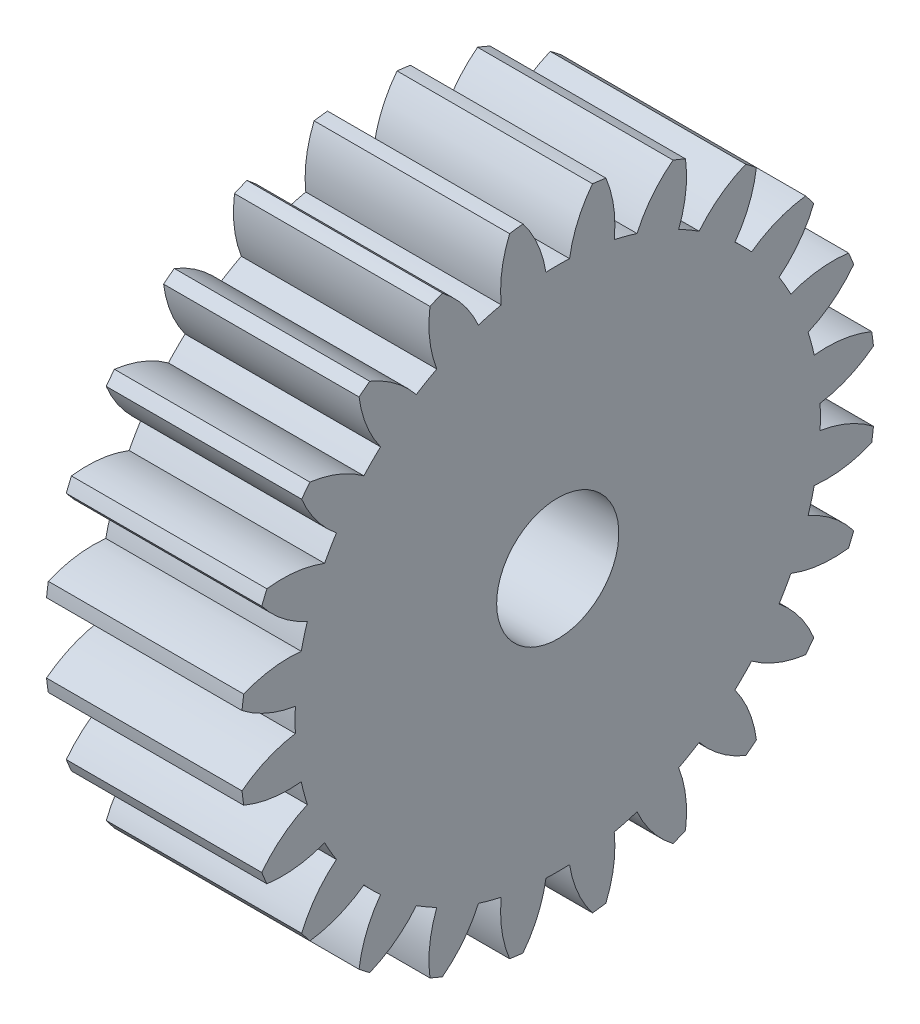
SolidWorks part; units mm, degrees
ref_plane "Plane1" through (0, 0, 0) normal (0, 0, 1) x (1, 0, 0)
ref_plane "Plane2" through (0, 0, 0) normal (0, 1, 0) x (1, 0, 0)
ref_plane "Plane3" through (0, 0, 0) normal (1, 0, 0) x (0, 0, -1)
sketch "HoldingSke" plane through (0, 0, 0) normal (0, 1, 0) x (1, 0, 0)
  line L0 (0, 0) -> (0.9135, -0.4067)
  line L1 (-15, 0) -> (100, 0) construction
  line L2 (0, 0) -> (-2.1039, 2.3779)
  line L3 (0, 0) -> (-11.863, 4.5341)
  line L4 (0, 0) -> (7.8894, 3.5126)
  line L5 (0, 0) -> (-46.8476, -17.4728)
  line L6 (0, 0) -> (-6.6317, -4.4744)
  line L7 (-2.1039, 2.3779) -> (8.6586, 51.2059)
  line L8 (-76.2, 54.61) -> (-75.3, 54.61)
  line L9 (-71.009, 38.7566) -> (-53.1078, 45.2721)
  line L10 (-76.2, 71.12) -> (104.1128, 71.12)
  line L11 (0, 0) -> (-8, 0)
  line L12 (-76.2, 101.6) -> (-76.162, 101.6)
  line L13 (24.9733, 27.94) -> (52.9518, 28.4284)
  line L14 (24.9733, 27.94) -> (24.9743, 27.94)
  line L15 (24.9733, 27.94) -> (100.4006, 29.5858)
  line L16 (-63.627, -1) -> (-12.827, -1)
  circle A0 centre (0, 0) radius 2.5
  circle A1 centre (0, 0) radius 10.749
  circle A2 centre (0, 0) radius 37.5
  circle A3 centre (0, 0) radius 2.5
  dimension "Num_teeth" = 24
  dimension "Pitch_radius" = 180.3128
  dimension "Width" = 8
  dimension "Thickness" = 8
sketch "BasProSke" plane through (0, 0, 0) normal (0, 1, 0) x (1, 0, 0)
  line L0 (-10, 0) -> (60, 0) construction
  line L1 (0, 0) -> (0, 13)
  line L2 (0, 0) -> (8, 0)
  line L3 (8, 0) -> (8, 13)
  line L4 (8, 13) -> (0, 13)
  dimension "Thickness" = 8
  dimension "Diameter" = 26
revolve "Base-Revolve" add sketch "BasProSke" angle 360 about L0
sketch "TooCutSke" plane through (0, 0, 0) normal (1, 0, 0) x (0, 0, -1)
  line L1 (0, 0) -> (0, 107) construction
  line L2 (0, 0) -> (-0.8513, 11.9698) construction
  line L3 (0, 0) -> (-3.127, 23.752) construction
  line L4 (-0.8513, 11.9698) -> (-1.5635, 11.876) construction
  arc A0 (0.4834, 10.7381) -> (-0.4834, 10.7381) centre (0, 0) ccw
  arc A1 (1.4409, 12.9455) -> (-1.4409, 12.9455) centre (0, 0) ccw
  circle A2 centre (0, 0) radius 12 construction
  circle A3 centre (0, 0) radius 11.2763 construction
  arc A4 (-0.4834, 10.7381) -> (-1.4409, 12.9455) centre (-5.2252, 9.9926) ccw
  arc A5 (1.4409, 12.9455) -> (0.4834, 10.7381) centre (5.2252, 9.9926) ccw
extrude "ToothCut" cut sketch "TooCutSke" along normal through all
fillet "Breaks" [suppressed] radius 0.02 tangent propagation no
fillet "RootFillets" [suppressed] radius 0.251
pattern_circular "TeethCuts" count 24 every 15 about axis through (-10, 0, 0) along (1, 0, 0) of "ToothCut", "RootFillets", "Breaks"
sketch "HubNeaOneSke" plane through (0, 0, 0) normal (-1, 0, 0) x (0, 0, 1)
  circle A0 centre (0, 0) radius 10.749
  dimension "Diameter" = 21.498
extrude "HubNearOne" [suppressed] add sketch "HubNeaOneSke" along normal blind 42.0001
sketch "HubNeaBotSke" plane through (0, 0, 0) normal (-1, 0, 0) x (0, 0, 1)
  circle A0 centre (0, 0) radius 10.749
  dimension "Diameter" = 21.498
extrude "HubNearBoth" [suppressed] add sketch "HubNeaBotSke" along normal blind 21
ref_plane "FarPln" through (8, 0, 0) normal (1, 0, 0) x (0, 0, -1)
sketch "HubFarSke" plane through (8, 0, 0) normal (1, 0, 0) x (0, 0, -1)
  circle A0 centre (0, 0) radius 10.749
  dimension "Diameter" = 21.498
extrude "HubFar" [suppressed] add sketch "HubFarSke" along normal blind 21
sketch "BorSke" plane through (0, 0, 0) normal (1, 0, 0) x (0, 0, -1)
  circle A0 centre (0, 0) radius 2.5
  dimension "Diameter" = 5
extrude "Bore" cut sketch "BorSke" along normal mid plane 100.0001
sketch "KeySke" plane through (0, 0, 0) normal (1, 0, 0) x (0, 0, -1)
  line L0 (-1, 0) -> (-1, 3.4)
  line L1 (-1, 3.4) -> (1, 3.4)
  line L2 (1, 3.4) -> (1, 0)
  line L3 (0, 0) -> (0, 34) construction
  line L4 (-1, 0) -> (1, 0)
  dimension "Width" = 2
extrude "Keyway" [suppressed] cut sketch "KeySke" along normal mid plane 100.0001
pattern_circular "Keyway2" [suppressed] count 2 every 90 about axis through (-10, 0, 0) along (1, 0, 0)
equation "' \"Module@HoldingSke\" = 6.35"
equation "' \"Num_teeth@HoldingSke\" = 12"
equation "' \"Ap@HoldingSke\" =  20"
equation "' \"Ap@HoldingSke\" = 20"
equation "' \"Width@HoldingSke\" = 0.5 * 25.4"
equation "' \"Hub_dia@HoldingSke\"= 1 * 25.4"
equation "' \"Hub_dia@HoldingSke\" = 1 * 25.4"
equation "' \"Overall_len@HoldingSke\" = 1.0 * 25.4"
equation "' \"Bore@HoldingSke\" = 0.75 * 25.4"
equation "' \"T_dim@HoldingSke\" = 0.1 * 25.4"
equation "' \"Width@KeySke\" = 0.25 * 25.4"
equation "' \"Show_teeth@HoldingSke\" = 13"
equation "' \"Backlash@HoldingSke\" = 0.009 * 25.4"
equation "' \"Addendum_fac@HoldingSke\" = 1.0"
equation "' \"Dedendum_fac@HoldingSke\" = 1.25"
equation "' \"Dedendum_add@HoldingSke\" = 0.00005 * 25.4"
equation "' \"Clearance_fac@HoldingSke\" = 0.25"
equation "\"Pitch@HoldingSke\" = 1 / \"Module@HoldingSke\""
equation "\"Overcut_dia@TooCutSke\" = (\"Num_teeth@HoldingSke\" + 2 * \"Addendum_fac@HoldingSke\") / \"Pitch@HoldingSke\" + 0.002 * 25.4"
equation "\"Pitch_dia@TooCutSke\" = \"Num_teeth@HoldingSke\" / \"Pitch@HoldingSke\""
equation "\"Base_dia@TooCutSke\" = \"Num_teeth@HoldingSke\" / \"Pitch@HoldingSke\" * cos((\"Ap@HoldingSke\"  * 3.14159265 / 180))"
equation "\"Root_dia@TooCutSke\" = (\"Num_teeth@HoldingSke\" + 2) / \"Pitch@HoldingSke\" - 2 * (\"Addendum_fac@HoldingSke\" + \"Dedendum_fac@HoldingSke\") / \"Pitch@HoldingSke\" - \"Dedendum_add@HoldingSke\" * 2"
equation "\"Half_ang@TooCutSke\" = 180 / \"Num_teeth@HoldingSke\""
equation "\"Half_CT@TooCutSke\" = \"Num_teeth@HoldingSke\" / \"Pitch@HoldingSke\" * sin((3.14159265 / 2 / \"Num_teeth@HoldingSke\")) / 2 - 7 * \"Backlash@HoldingSke\" / 4"
equation "\"Flank_rad@TooCutSke\" = \"Num_teeth@HoldingSke\" / \"Pitch@HoldingSke\" / 5"
equation "\"Radius@RootFillets\" = \"Clearance_fac@HoldingSke\" / \"Pitch@HoldingSke\" + \"Dedendum_add@HoldingSke\""
equation "\"Break_rad@Breaks\" = 0.02 / \"Pitch@HoldingSke\""
equation "\"Thickness@HoldingSke\" = \"Width@HoldingSke\""
equation "\"OAL@HoldingSke\" = \"Thickness@HoldingSke\""
equation "\"MHD@HoldingSke\" = (\"Num_teeth@HoldingSke\" + 2) / \"Pitch@HoldingSke\" - 2 * (\"Addendum_fac@HoldingSke\" + \"Dedendum_fac@HoldingSke\")  / \"Pitch@HoldingSke\" - \"Dedendum_add@HoldingSke\" * 2"
equation "\"MBD@HoldingSke\" = (\"Num_teeth@HoldingSke\" + 2) / \"Pitch@HoldingSke\" - 2 * (\"Addendum_fac@HoldingSke\" + \"Dedendum_fac@HoldingSke\")  / \"Pitch@HoldingSke\" - \"Dedendum_add@HoldingSke\" * 2 - 0.002 * 25.4"
equation "\"MHD@HoldingSke\" = ((sgn( \"MHD@HoldingSke\" - \"Hub_dia@HoldingSke\" )-1)*( \"MHD@HoldingSke\" - \"Hub_dia@HoldingSke\" ))/-2+ \"Hub_dia@HoldingSke\""
equation "\"MBD@HoldingSke\" = ((sgn( \"MBD@HoldingSke\" - \"Bore@HoldingSke\" )-1)*( \"MBD@HoldingSke\" - \"Bore@HoldingSke\" ))/-2+ \"Bore@HoldingSke\""
equation "\"OAL@HoldingSke\" = ((sgn( \"OAL@HoldingSke\" - \"Overall_len@HoldingSke\" )+1)*( \"OAL@HoldingSke\" - \"Overall_len@HoldingSke\" ))/2 + \"Overall_len@HoldingSke\" + 0.000002 * 25.4"
equation "\"Num_teeth@TeethCuts\" = int( \"Show_teeth@HoldingSke\" ) + 1"
equation "\"Num_teeth@TeethCuts\" = ((sgn( \"Num_teeth@TeethCuts\" - \"Num_teeth@HoldingSke\" )-1)*( \"Num_teeth@TeethCuts\" - \"Num_teeth@HoldingSke\" ))/-2+ \"Num_teeth@HoldingSke\""
equation "\"Num_teeth@TeethCuts\" = ((sgn( \"Num_teeth@TeethCuts\" - 2.0)+1)*( \"Num_teeth@TeethCuts\" - 2.0))/2 +2.0"
equation "\"Angle@TeethCuts\" = 360.0 / \"Num_teeth@HoldingSke\""
equation "\"Diameter@BasProSke\" = (\"Num_teeth@HoldingSke\" + 2 * \"Addendum_fac@HoldingSke\") / \"Pitch@HoldingSke\""
equation "\"Thickness@BasProSke\"  = \"Thickness@HoldingSke\""
equation "' \"Fillet_rad@BasProSke\" =  \"Thickness@HoldingSke\" * 0.05"
equation "' \"Fillet_rad@BasProSke\" = \"Thickness@HoldingSke\" * 0.05"
equation "\"MHD@HoldingSke\" = ((sgn( \"MHD@HoldingSke\" - \"Root_dia@TooCutSke\" )-1)*( \"MHD@HoldingSke\" - \"Root_dia@TooCutSke\" ))/-2+ \"Root_dia@TooCutSke\""
equation "\"Diameter@HubNeaOneSke\" = \"MHD@HoldingSke\""
equation "\"Length@HubNearOne\" = \"OAL@HoldingSke\" - \"Thickness@BasProSke\""
equation "\"Diameter@HubNeaBotSke\" = \"MHD@HoldingSke\""
equation "\"Length@HubNearBoth\" = ( \"OAL@HoldingSke\" - \"Thickness@BasProSke\" ) / 2.0"
equation "\"Thickness@FarPln\" = \"Thickness@BasProSke\""
equation "\"Diameter@HubFarSke\" = \"MHD@HoldingSke\""
equation "\"Length@HubFar\" = ( \"OAL@HoldingSke\" - \"Thickness@BasProSke\" ) / 2.0"
equation "\"Diameter@BorSke\" = \"MBD@HoldingSke\""
equation "\"D1@Bore\" = \"OAL@HoldingSke\" * 2.0"
equation "\"D1@Keyway\" = \"OAL@HoldingSke\" * 2.0"
equation "\"Offset@KeySke\" = \"T_dim@HoldingSke\" + \"MBD@HoldingSke\" / 2.0"
